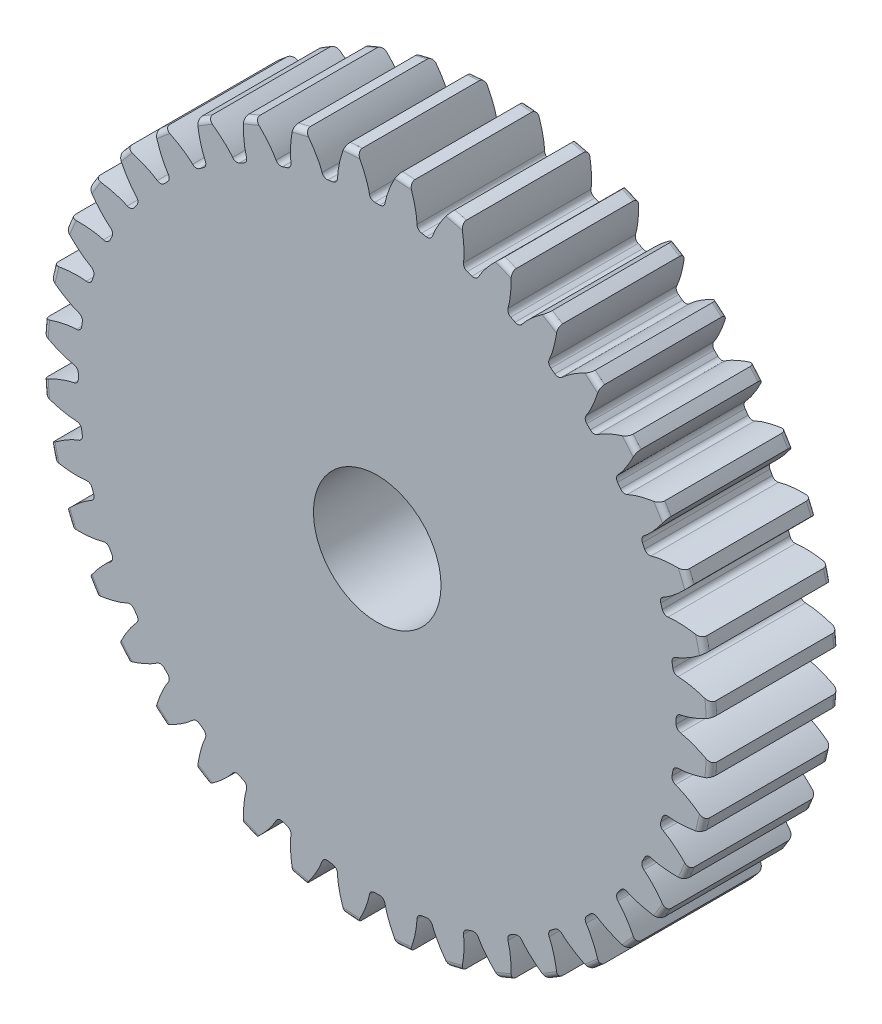
SolidWorks part; units mm, degrees
ref_plane "Front Plane" through (0, 0, 0) normal (0, 0, 1) x (1, 0, 0)
ref_plane "Top Plane" through (0, 0, 0) normal (0, 1, 0) x (1, 0, 0)
ref_plane "Right Plane" through (0, 0, 0) normal (1, 0, 0) x (0, 0, -1)
sketch "Sketch1" plane through (0, 0, 0) normal (0, 0, 1) x (1, 0, 0)
  line L0 (0, 0) -> (0, 15.875) construction
  line L1 (-5.1021, 17.732) -> (5.1021, 14.018) construction
  circle A0 centre (0, 0) radius 14.8828 construction
  circle A1 centre (0, 0) radius 16.6687 construction
  circle A2 centre (0, 0) radius 15.875 construction
  circle A3 centre (0, 0) radius 14.9176 construction
  circle A4 centre (0, 0) radius 3.175 construction
  circle A5 centre (0, 0) radius 9.144 construction
  point P8 (406.4, 0)
  point P13 (508, 0)
  dimension "OD | Outside Diameter" = 33.3375
  dimension "Root Diameter" = 29.7656
  dimension "Gear Pitch Diameter" = 31.75
  dimension "Base Diameter" = 29.8352
  dimension "For Shaft Diameter" = 6.35
  dimension "Hub Diameter" = 18.288
  dimension "Pressure Angle" = 20
  dimension "Number of Teeth" = 1016
  dimension "Gear Pitch | Diametral Pitch" = 812.8
sketch "Sketch2" plane through (0, 0, 0) normal (1, 0, 0) x (0, 0, -1)
  line L0 (-7.1374, 0) -> (7.1374, 0) construction
  line L1 (-6.35, 16.6687) -> (6.35, 16.6687) construction
  line L2 (0, 55) -> (0, -55) construction
  point P2 (0, 16.6687)
  point P4 (0.7874, 0)
  point P6 (0.7874, 16.6687)
  point P9 (0, 0)
  point P10 (5.5626, 16.6687)
  point P11 (5.5626, 0)
  point P12 (4.6795, 16.6687)
  point P15 (0, 0)
  dimension "D1" = 6.35
  dimension "D2" = 6.35
sketch "Sketch3" plane through (0, 0, 0) normal (0, 0, 1) x (1, 0, 0)
  circle A0 centre (0, 0) radius 16.6687
  circle A1 centre (0, 0) radius 16.6687 construction
extrude "Boss-Extrude1" add sketch "Sketch3" against normal up to vertex (7.1374 mm away) and the other way up to vertex (7.1374 mm away) up to point (0, 0, -7.1374) other way up to point (0, 0, 7.1374)
sketch "Sketch5" plane through (0, 0, 0) normal (1, 0, 0) x (0, 0, -1)
  line L1 (-7.1374, 16.6687) -> (0.7874, 16.6687)
  line L2 (-7.1374, 16.6687) -> (-7.1374, 9.144)
  line L3 (-7.1374, 9.144) -> (0.7874, 9.144)
  line L4 (0.7874, 16.6687) -> (0.7874, 9.144)
  line L11 (7.1374, 3.175) -> (-7.1374, 3.175)
  line L12 (7.1374, 3.175) -> (7.1374, 0)
  line L13 (7.1374, 0) -> (-7.1374, 0)
  line L14 (-7.1374, 3.175) -> (-7.1374, 0)
  point P5 (0, 3.175)
  point P12 (0, 9.144)
revolve "Cut-Revolve1" cut sketch "Sketch5" angle 360 about L0
fillet "Fillet2" radius 0.2663 6 edges at (16.6687, 0, -7.1374) (3.175, 0, -7.1374) (3.175, 0, 7.1374) (9.144, 0, -0.7874) (16.6687, 0, -0.7874) (9.144, 0, 7.1374)
sketch "Sketch4" plane through (0, 0, 0) normal (0, 0, 1) x (1, 0, 0)
  line L0 (0, 0) -> (14.8784, 0.3626) construction
  line L2 (0, 0) -> (14.8784, -0.3626) construction
  line L4 (14.8784, 0.3626) -> (14.9132, 0.3634)
  line L5 (14.9132, -0.3634) -> (14.8784, -0.3626)
  arc A0 (14.8784, 0.3626) -> (14.8784, -0.3626) centre (0, 0) cw
  arc A3 (16.6383, 1.0067) -> (16.6383, -1.0067) centre (0, 0) cw
  circle A4 centre (0, 0) radius 16.6687 construction
  spline S0 degree 4 poles (14.9132, 0.3634) (14.9159, 0.3635) (14.9236, 0.3639) (14.9381, 0.3649) (14.9618, 0.3671) (14.9919, 0.3706) (15.0308, 0.376) (15.0766, 0.3835) (15.1268, 0.3928) (15.1814, 0.4042) (15.2358, 0.4166) (15.29, 0.4301) (15.3439, 0.4444) (15.4091, 0.4628) (15.4872, 0.4863) (15.5783, 0.516) (15.6814, 0.5524) (15.7862, 0.5921) (15.8891, 0.6335) (15.9927, 0.678) (16.0929, 0.7228) (16.1965, 0.7721) (16.2921, 0.8189) (16.3988, 0.8743) (16.4848, 0.9199) (16.5978, 0.9832) (16.6645, 1.0215) (16.7423, 1.0675) (16.7768, 1.0885) (16.798, 1.1014) knots 0 0 0 0 0 0.005377 0.015084 0.028532 0.04661 0.064855 0.092111 0.119476 0.146842 0.174209 0.201575 0.228941 0.256307 0.307035 0.361767 0.4165 0.471232 0.525964 0.580697 0.635429 0.690161 0.744894 0.799626 0.854358 0.909091 0.954545 1 1 1 1 1 construction
  spline S1 degree 4 poles (14.9132, 0.3634) (14.9159, 0.3635) (14.9236, 0.3639) (14.9381, 0.3649) (14.9618, 0.3671) (14.9919, 0.3706) (15.0308, 0.376) (15.0766, 0.3835) (15.1268, 0.3928) (15.1814, 0.4042) (15.2358, 0.4166) (15.29, 0.4301) (15.3439, 0.4444) (15.4091, 0.4628) (15.4872, 0.4863) (15.5783, 0.516) (15.6814, 0.5524) (15.7862, 0.5921) (15.8891, 0.6335) (15.9927, 0.678) (16.0929, 0.7228) (16.1965, 0.7721) (16.2921, 0.8189) (16.3988, 0.8743) (16.4848, 0.9199) (16.5733, 0.9695) (16.6163, 0.994) (16.6383, 1.0067) knots 0 0 0 0 0 0.005377 0.015084 0.028532 0.04661 0.064855 0.092111 0.119476 0.146842 0.174209 0.201575 0.228941 0.256307 0.307035 0.361767 0.4165 0.471232 0.525964 0.580697 0.635429 0.690161 0.744894 0.799626 0.854358 0.909091 0.909091 0.909091 0.909091 0.909091
  spline S2 degree 4 poles (14.9132, -0.3634) (14.9159, -0.3635) (14.9236, -0.3639) (14.9381, -0.3649) (14.9618, -0.3671) (14.9919, -0.3706) (15.0308, -0.376) (15.0766, -0.3835) (15.1268, -0.3928) (15.1814, -0.4042) (15.2358, -0.4166) (15.29, -0.4301) (15.3439, -0.4444) (15.4091, -0.4628) (15.4872, -0.4863) (15.5783, -0.516) (15.6814, -0.5524) (15.7862, -0.5921) (15.8891, -0.6335) (15.9927, -0.678) (16.0929, -0.7228) (16.1965, -0.7721) (16.2921, -0.8189) (16.3988, -0.8743) (16.4848, -0.9199) (16.5978, -0.9832) (16.6645, -1.0215) (16.7423, -1.0675) (16.7768, -1.0885) (16.798, -1.1014) knots 0 0 0 0 0 0.005377 0.015084 0.028532 0.04661 0.064855 0.092111 0.119476 0.146842 0.174209 0.201575 0.228941 0.256307 0.307035 0.361767 0.4165 0.471232 0.525964 0.580697 0.635429 0.690161 0.744894 0.799626 0.854358 0.909091 0.954545 1 1 1 1 1 construction
  spline S3 degree 4 poles (14.9132, -0.3634) (14.9159, -0.3635) (14.9236, -0.3639) (14.9381, -0.3649) (14.9618, -0.3671) (14.9919, -0.3706) (15.0308, -0.376) (15.0766, -0.3835) (15.1268, -0.3928) (15.1814, -0.4042) (15.2358, -0.4166) (15.29, -0.4301) (15.3439, -0.4444) (15.4091, -0.4628) (15.4872, -0.4863) (15.5783, -0.516) (15.6814, -0.5524) (15.7862, -0.5921) (15.8891, -0.6335) (15.9927, -0.678) (16.0929, -0.7228) (16.1965, -0.7721) (16.2921, -0.8189) (16.3988, -0.8743) (16.4848, -0.9199) (16.5733, -0.9695) (16.6163, -0.994) (16.6383, -1.0067) knots 0 0 0 0 0 0.005377 0.015084 0.028532 0.04661 0.064855 0.092111 0.119476 0.146842 0.174209 0.201575 0.228941 0.256307 0.307035 0.361767 0.4165 0.471232 0.525964 0.580697 0.635429 0.690161 0.744894 0.799626 0.854358 0.909091 0.909091 0.909091 0.909091 0.909091
  dimension "D1" = 29.7656
extrude "Cut-Extrude1" cut sketch "Sketch4" against normal through all both and the other way through all
fillet "Fillet1" radius 0.2663 2 edges at (14.8784, -0.3626, -3.9624) (14.8784, 0.3626, -3.9624)
pattern_circular "CirPattern1" count 40 over 360 about axis through (0, 0, 7.1374) along (0, 0, -1) of "Cut-Extrude1", "Fillet1"
sketch "Sketch6" plane through (0, 0, 0) normal (0, 1, 0) x (1, 0, 0)
  line L0 (-12.1935, 0.7874) -> (-10.9517, 0.7874) construction
  line L1 (-11.5726, 0.7874) -> (13.0937, 0.7874)
  line L2 (-11.5726, 0.7874) -> (-11.5726, -9.5826)
  line L3 (-11.5726, -9.5826) -> (13.0937, -9.5826)
  line L4 (13.0937, 0.7874) -> (13.0937, -9.5826)
extrude "Cut-Extrude2" cut sketch "Sketch6" against normal through all both and the other way through all
equation "\"Root Diameter@Sketch1\"=\"Root Diameter\""
equation "\"OD | Outside Diameter@Sketch1\"=\"Outside Diameter\""
equation "\"D1@CirPattern1\"=\"Number of Teeth\""
equation "\"Diametral Pitch\"=32"
equation "\"Number of Teeth\"= 40"
equation "\"Pressure Angle\"=20"
equation "\"Pitch Diameter\"= \"Number of Teeth\" / \"Diametral Pitch\""
equation "\"Base Diameter\"= \"Pitch Diameter\" * cos ( \"Pressure Angle\" )"
equation "\"Outside Diameter\"= ( \"Number of Teeth\" + 2 ) / \"Diametral Pitch\""
equation "\"Dedendum\"= 1.25 / \"Diametral Pitch\""
equation "\"Root Diameter\"= \"Pitch Diameter\" - ( 2 * \"Dedendum\" )"
equation "\"Pitch Angle\"= 360deg / \"Number of Teeth\""
equation "\"Alpha\"= sqr ( \"Pitch Diameter\" ^ 2 - \"Base Diameter\" ^ 2 ) / \"Base Diameter\" * 180 / PI - \"Pressure Angle\""
equation "\"Beta\"= ( \"Pitch Angle\" / 4 - \"Alpha\" )"
equation "\"Phi\"= sqr ( ( \"Outside Diameter\" / 2 ) ^ 2 - ( \"Base Diameter\" / 2 ) ^ 2 ) / ( \"Base Diameter\" / 2 )"
equation "\"Addendum\"= 1 / \"Diametral Pitch\""
equation "\"WorkingDepth\"= 2 / \"Diametral Pitch\""
equation "\"WholeDepth\"= 2.25 / \"Diametral Pitch\""
equation "\"Clearance\"= 0.25 / \"Diametral Pitch\""
equation "\"ToothThickness\"= ( pi * 2 ) / \"Diametral Pitch\""
equation "\"CircularPitch\"= pi / \"Diametral Pitch\""
equation "\"Number of Teeth@Sketch1\"=\"Number of Teeth\""
equation "\"Gear Pitch | Diametral Pitch@Sketch1\"=\"Diametral Pitch\""
equation "\"Pressure Angle@Sketch1\"=\"Pressure Angle\""
equation "\"Gear Pitch Diameter@Sketch1\"=\"Pitch Diameter\""
equation "\"Base Diameter@Sketch1\"=\"Base Diameter\""
equation "\"Fillet\"= \"Clearance\" * cos ( \"Pressure Angle\" ) * tan ( ( 90 + \"Pressure Angle\" ) / 2 )"
equation "\"D1@Fillet1\"=\"Fillet\""
equation "\"D1@Sketch4\"=if( \"Base Diameter\">\"Root Diameter\",\"Root Diameter\",\"Base Diameter\"-.00001)"
equation "\"D1@Fillet2\"=\"Fillet\""
